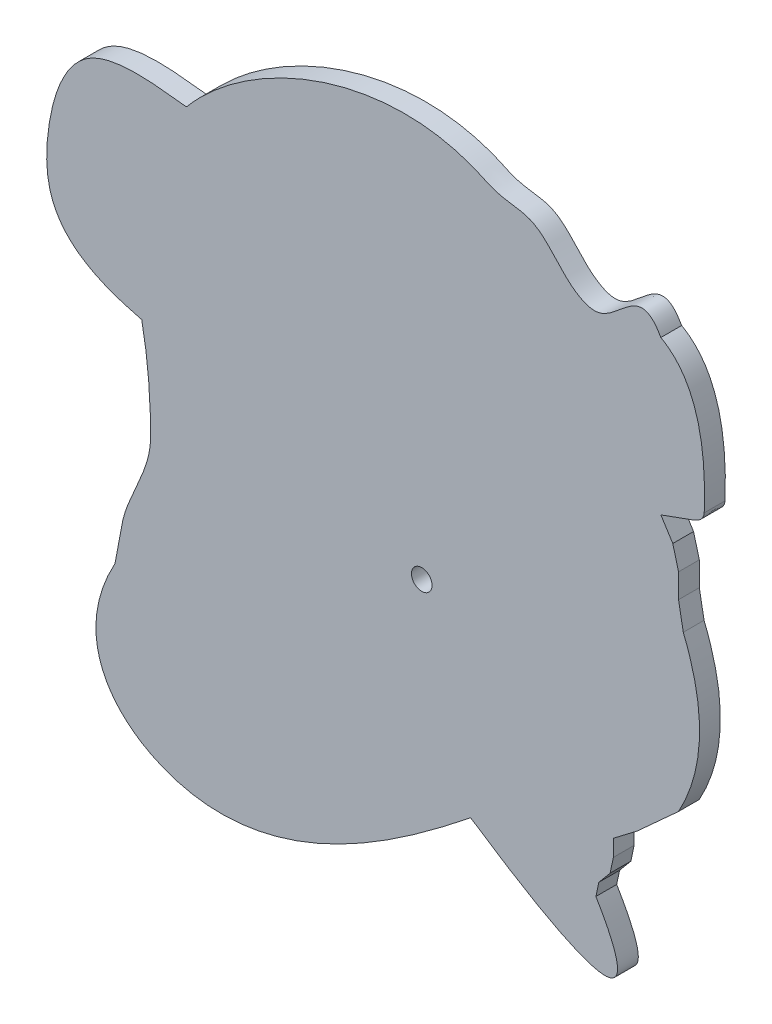
SolidWorks part; units mm, degrees
ref_plane "Front Plane" through (0, 0, 0) normal (0, 0, 1) x (1, 0, 0)
ref_plane "Top Plane" through (0, 0, 0) normal (0, 1, 0) x (1, 0, 0)
ref_plane "Right Plane" through (0, 0, 0) normal (1, 0, 0) x (0, 0, -1)
sketch "Sketch1" plane through (0, 0, 0) normal (0, 0, 1) x (1, 0, 0)
  line L0 (134.6667, 500.5) -> (673.3333, 500.5) construction
  line L9 (158.8486, 158.066) -> (159.2873, 160.158)
  line L10 (159.2873, 160.158) -> (161.0243, 162.2425)
  line L11 (161.0243, 162.2425) -> (161.5128, 164.5724)
  line L12 (161.5128, 164.5724) -> (161.5128, 167.1023)
  line L13 (161.5128, 167.1023) -> (165.1835, 169.9013)
  line L14 (165.1835, 169.9013) -> (171.472, 175.6217)
  line L15 (86.5908, 171.7678) -> (85.3882, 165.3811)
  line L16 (168.7713, 213.5075) -> (170.5915, 210.6336)
  line L17 (170.5915, 210.6336) -> (171.472, 207.3286)
  line L18 (171.472, 207.3286) -> (171.472, 203.6405)
  line L19 (171.472, 203.6405) -> (172.1964, 199.6877)
  line L21 (168.7713, 213.5075) -> (173.7621, 215.3232)
  circle A0 centre (132.2467, 186.7018) radius 1.5748
  spline S0 degree 3 poles (85.3882, 165.3811) (78.0487, 152.0358) (100.0626, 129.8424) (127.3192, 149.0039) (139.7108, 158.9096) knots 0 0 0 0 0.355984 1 1 1 1
  spline S1 degree 2 poles (139.7108, 158.9096) (170.7543, 138.1113) (158.8486, 158.066) knots 0 0 0 1 1 1
  spline S2 degree 3 poles (89.473, 199.6877) (76.4141, 202.7784) (72.921, 212.6954) (79.1309, 233.8673) (92.3571, 231.6545) (96.3054, 231.2529) knots 0 0 0 0 0.435393 0.719887 1 1 1 1
  spline S3 degree 2 poles (168.7713, 236.9728) (176.0245, 232.9136) (175.3973, 217.0895) knots 0 0 0 1 1 1
  spline S4 degree 2 poles (173.7621, 215.3232) (175.2991, 215.89) (175.3973, 217.0895) knots 0 0 0 1 1 1
  spline S5 degree 3 poles (168.7713, 236.9728) (165.3483, 243.1818) (161.713, 233.5905) (153.5919, 237.311) (150.5622, 243.2925) (144.2663, 243.1727) (127.5396, 251.7095) (106.0894, 242.9451) (96.3054, 231.2529) knots 0 0 0 0 0.145953 0.187032 0.301265 0.367852 0.402075 1 1 1 1
  spline S11 degree 2 poles (172.1964, 199.6877) (177.5125, 186.6119) (171.472, 175.6217) knots 0 0 0 1 1 1
  spline S12 degree 3 poles (89.473, 199.6877) (90.4497, 194.8375) (90.826, 189.8378) (90.8383, 180.2807) (87.6783, 176.1914) (86.5908, 171.7678) knots 0 0 0 0 0.517811 0.520823 1 1 1 1
extrude "Boss-Extrude2" add sketch "Sketch1" along normal blind 3.175
